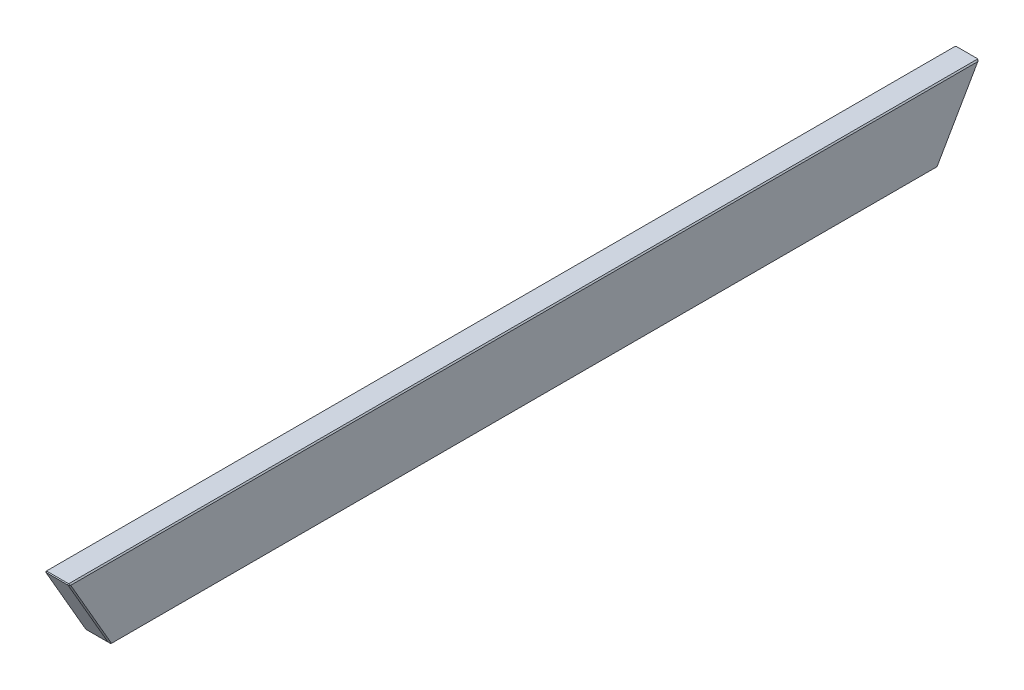
SolidWorks part; units mm, degrees
ref_plane "Front Plane" through (0, 0, 0) normal (0, 0, 1) x (1, 0, 0)
ref_plane "Top Plane" through (0, 0, 0) normal (0, 1, 0) x (1, 0, 0)
ref_plane "Right Plane" through (0, 0, 0) normal (1, 0, 0) x (0, 0, -1)
sketch "Sketch1" plane through (0, 0, 0) normal (0, 0, 1) x (1, 0, 0)
  line L1 (-1.05, -3.125) -> (1.05, -3.125)
  line L2 (-1.05, -3.125) -> (-1.05, 3.125)
  line L3 (-1.05, 3.125) -> (1.05, 3.125)
  line L4 (1.05, -3.125) -> (1.05, 3.125)
  line L5 (-1.05, -3.125) -> (1.05, 3.125) construction
  line L6 (-1.05, 3.125) -> (1.05, -3.125) construction
  point P0 (0, 0)
  dimension "D1" = 6.25
  dimension "D2" = 2.1
extrude "Boss-Extrude1" add sketch "Sketch1" along normal mid plane 78
draft "Draft1" type of draft neutral plane draft angle 30 faces to draft 1 face at (0, 0, 39) neutral plane through (-1.05, 3.125, 39) neutral plane normal (0, 1, 0) reverse direction yes parameters "D1"=30
draft "Draft2" type of draft neutral plane draft angle 30 faces to draft 1 face at (0, 0, -39) neutral plane through (-1.05, 3.125, 39) neutral plane normal (0, 1, 0) reverse direction yes parameters "D1"=30
chamfer "Chamfer1" distance 0.1 angle 45 4 edges at (-1.05, -3.125, 0) (1.05, -3.125, 0) (-1.05, 3.125, 0) (1.05, 3.125, 0)
chamfer "Chamfer2" distance 0.1 angle 45 14 edges at (1, -3.075, -35.4204) (1.05, 0, -37.1958) (1, 3.075, -38.9711) (0, 3.125, -39) (-1, 3.075, -38.9711) (-1.05, 0, -37.1958) (-1, -3.075, -35.4204) (0, -3.125, -35.3916) (-1, 3.075, 38.9711) (0, 3.125, 39) (1, 3.075, 38.9711) (1.05, 0, 37.1958) (0, -3.125, 35.3916) (-1.05, 0, 37.1958)
